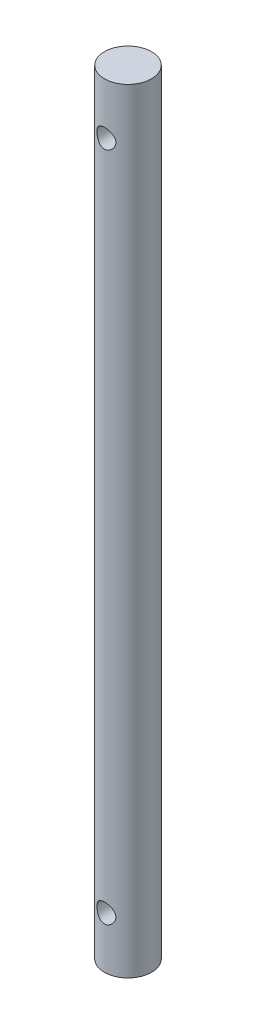
SolidWorks part; units mm, degrees
material "Plain Carbon Steel"
ref_plane "Front Plane" through (0, 0, 0) normal (0, 0, 1) x (1, 0, 0)
ref_plane "Top Plane" through (0, 0, 0) normal (0, 1, 0) x (1, 0, 0)
ref_plane "Right Plane" through (0, 0, 0) normal (1, 0, 0) x (0, 0, -1)
sketch "Sketch1" plane through (0, 0, 0) normal (0, 1, 0) x (1, 0, 0)
  circle A0 centre (0, 0) radius 3.96
  dimension "D1" = 7.92
extrude "Boss-Extrude1" add sketch "Sketch1" along normal mid plane 130.18
ref_plane "Plane1" through (0, 56.43, 0) normal (0, 1, 0) x (1, 0, 0)
ref_axis "Axis1" through (0, 65.09, 0) along (0, -1, 0)
sketch "Sketch2" plane through (0, 0, 0) normal (0, 0, 1) x (1, 0, 0)
  line L0 (4.356, 56.43) -> (-4.356, 56.43) construction
  circle A0 centre (0, 56.43) radius 1.59
extrude "Cut-Extrude1" cut sketch "Sketch2" against normal through all both and the other way through all
mirror "Mirror1" about plane through (0, 0, 0) normal (0, 1, 0) of "Cut-Extrude1"
